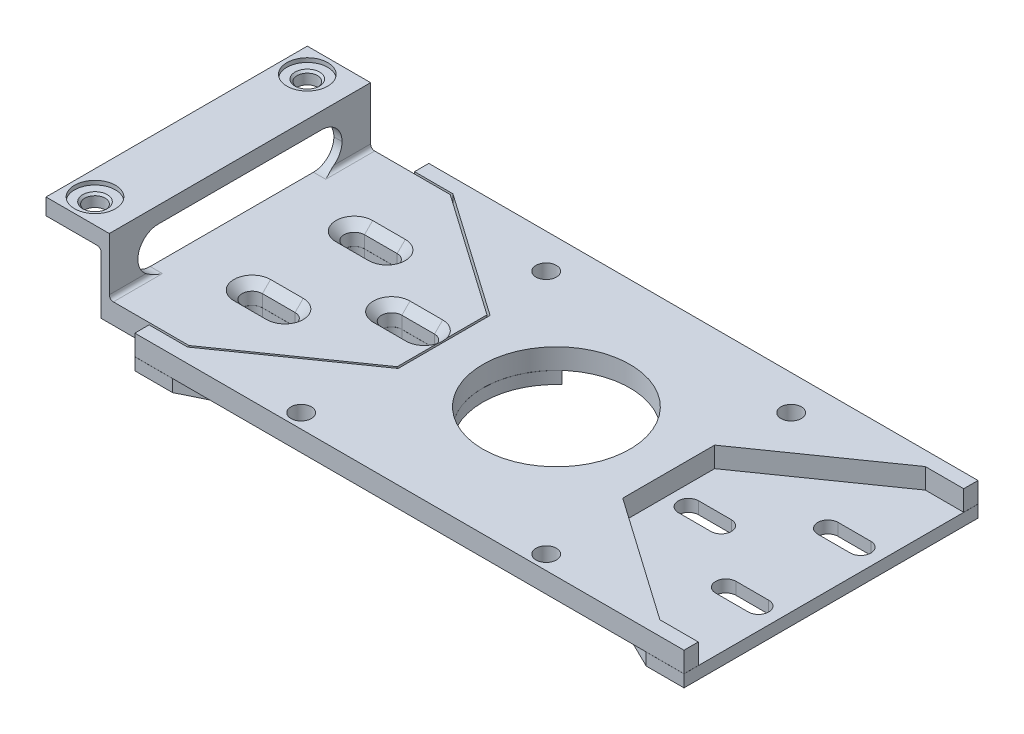
SolidWorks part; units mm, degrees
ref_plane "Front Plane" through (0, 0, 0) normal (0, 0, 1) x (1, 0, 0)
ref_plane "Top Plane" through (0, 0, 0) normal (0, 1, 0) x (1, 0, 0)
ref_plane "Right Plane" through (0, 0, 0) normal (1, 0, 0) x (0, 0, -1)
sketch "Sketch1" plane through (0, 0, 0) normal (0, 1, 0) x (1, 0, 0)
  line L0 (0, 40.64) -> (38.1, 13.9621)
  line L1 (-44.45, -40.64) -> (0, -40.64)
  line L2 (-44.45, -40.64) -> (-44.45, 40.64)
  line L3 (-44.45, 40.64) -> (0, 40.64)
  line L4 (38.1, -13.9621) -> (38.1, 13.9621)
  line L5 (-5.08, 19.05) -> (5.08, 19.05)
  line L6 (-5.08, 12.7) -> (5.08, 12.7)
  line L7 (0, -40.64) -> (38.1, -13.9621)
  line L8 (-5.08, -12.7) -> (5.08, -12.7)
  line L9 (-5.08, -19.05) -> (5.08, -19.05)
  line L10 (22.4163, 3.175) -> (32.5763, 3.175)
  line L11 (22.4163, -3.175) -> (32.5763, -3.175)
  circle A0 centre (-36.83, 33.02) radius 3.175
  circle A1 centre (-36.83, -33.02) radius 3.175
  arc A5 (5.08, 12.7) -> (5.08, 19.05) centre (5.08, 15.875) ccw
  arc A6 (-5.08, 19.05) -> (-5.08, 12.7) centre (-5.08, 15.875) ccw
  arc A7 (5.08, -19.05) -> (5.08, -12.7) centre (5.08, -15.875) ccw
  arc A8 (-5.08, -12.7) -> (-5.08, -19.05) centre (-5.08, -15.875) ccw
  arc A9 (22.4163, 3.175) -> (22.4163, -3.175) centre (22.4163, 0) ccw
  arc A10 (32.5763, -3.175) -> (32.5763, 3.175) centre (32.5763, 0) ccw
  point P0 (0, 0)
  point P4 (38.1, 0)
  dimension "D1" = 6.35
  dimension "D2" = 66.04
  dimension "D3" = 7.62
  dimension "D4" = 7.62
  dimension "D5" = 7.62
  dimension "D6" = 38.1
  dimension "D7" = 145
  dimension "D8" = 145
  dimension "D9" = 44.45
extrude "Boss-Extrude1" add sketch "Sketch1" along normal blind 6.35
sketch "Sketch10" plane through (0, 6.35, 0) normal (0, 1, 0) x (1, 0, 0)
  line L1 (-44.45, 40.64) -> (-24.765, 40.64)
  line L2 (-44.45, 40.64) -> (-44.45, -40.64)
  line L3 (-44.45, -40.64) -> (-24.765, -40.64)
  line L4 (-24.765, -40.64) -> (-24.765, 40.64)
  circle A0 centre (-36.83, -33.02) radius 3.175 construction
  circle A1 centre (-36.83, 33.02) radius 3.175 construction
  circle A2 centre (-36.83, -33.02) radius 3.175
  circle A3 centre (-36.83, 33.02) radius 3.175
  dimension "D1" = 19.685
extrude "Boss-Extrude4" add sketch "Sketch10" along normal blind 17.78
sketch "Sketch12" plane through (0, 0, 0) normal (0, -1, 0) x (1, 0, 0)
  line L0 (0, -40.64) -> (-44.45, -40.64) construction
  line L1 (-44.45, 40.64) -> (-27.305, 40.64)
  line L2 (-44.45, 40.64) -> (-44.45, -40.64)
  line L3 (-44.45, -40.64) -> (-27.305, -40.64)
  line L5 (-27.305, 40.64) -> (-27.305, -40.64)
  line L6 (-44.45, 40.64) -> (0, 40.64) construction
  point P9 (-22.225, 40.64)
  dimension "D1" = 5.08
extrude "Cut-Extrude5" cut sketch "Sketch12" against normal blind 12.7
sketch "Sketch14" plane through (0, 24.13, 0) normal (0, 1, 0) x (1, 0, 0)
  circle A0 centre (-36.83, 33.02) radius 6.35
  circle A1 centre (-36.83, -33.02) radius 6.35
  dimension "D1" = 12.7
extrude "Cut-Extrude9" cut sketch "Sketch14" against normal blind 1.27
chamfer "Chamfer2" distance 0.635 angle 45 2 edges at (-36.83, 22.86, -29.845) (-36.83, 22.86, 36.195)
sketch "Sketch15" plane through (-24.765, 0, 0) normal (1, 0, 0) x (0, 0, -1)
  line L0 (-31.75, 6.35) -> (-31.75, 19.05)
  line L1 (-40.64, 6.35) -> (-13.9621, 6.35) construction
  line L2 (-31.75, 19.05) -> (31.75, 19.05)
  line L3 (31.75, 19.05) -> (31.75, 6.35)
  line L4 (13.9621, 6.35) -> (40.64, 6.35) construction
  line L5 (31.75, 6.35) -> (-31.75, 6.35)
  line L6 (-40.64, 24.13) -> (-40.64, 6.35) construction
  line L7 (40.64, 24.13) -> (40.64, 6.35) construction
  line L8 (-40.64, 24.13) -> (40.64, 24.13) construction
  dimension "D1" = 8.89
  dimension "D2" = 8.89
  dimension "D3" = 5.08
extrude "Cut-Extrude10" cut sketch "Sketch15" against normal blind 36.576
sketch "Sketch16" plane through (0, 0, -40.64) normal (0, 0, -1) x (-1, 0, 0)
  line L0 (27.305, 12.7) -> (27.305, 19.05)
  line L1 (27.305, 19.05) -> (44.45, 19.05)
  line L2 (44.45, 24.13) -> (44.45, 12.7) construction
  line L3 (44.45, 19.05) -> (44.45, 12.7)
  line L4 (44.45, 12.7) -> (27.305, 12.7)
  dimension "D1" = 5.08
extrude "Cut-Extrude11" cut sketch "Sketch16" against normal blind 84.836
fillet "Fillet1" radius 1.27 4 edges at (-27.305, 19.05, 36.195) (-27.305, 19.05, -36.195) (-24.765, 6.35, 36.195) (-24.765, 6.35, -36.195)
fillet "Fillet2" radius 6.35 4 edges at (-25.4, 6.35, 31.75) (-25.4, 6.35, -31.75) (-26.67, 19.05, -31.75) (-26.67, 19.05, 31.75)
chamfer "Chamfer3" distance 2.54 angle 45 12 edges at (0, 6.35, 19.05) (8.255, 6.35, 15.875) (-8.255, 6.35, 15.875) (0, 6.35, 12.7) (27.4963, 6.35, 3.175) (35.7513, 6.35, 0) (19.2413, 6.35, 0) (27.4963, 6.35, -3.175) (0, 6.35, -12.7) (8.255, 6.35, -15.875) (-8.255, 6.35, -15.875) (0, 6.35, -19.05)
sketch "Sketch18" plane through (0, 6.35, 0) normal (0, 1, 0) x (1, 0, 0)
  line L0 (-24.765, 60.325) -> (-24.765, -60.325) construction
  line L1 (-24.765, 60.325) -> (172.085, 60.325) construction
  line L2 (-24.765, -60.325) -> (172.085, -60.325) construction
  line L3 (172.085, -60.325) -> (172.085, 60.325) construction
  line L4 (73.66, 60.325) -> (73.66, 34.925) construction
  line L5 (-24.765, 34.925) -> (35.56, 34.925) construction
  line L6 (35.56, 34.925) -> (111.76, 34.925) construction
  line L7 (35.56, 34.925) -> (35.56, -41.275) construction
  line L8 (-11.7475, 45.72) -> (-11.7475, 41.275)
  line L9 (-11.7475, -45.72) -> (159.0675, -45.72)
  line L10 (-23.495, -40.64) -> (0, -40.64) construction
  line L11 (-11.7475, 45.72) -> (159.0675, 45.72)
  line L12 (159.0675, 45.72) -> (159.0675, 41.275)
  line L47 (-11.7475, -41.275) -> (-11.7475, -45.72)
  line L48 (73.66, 45.72) -> (73.66, -45.72) construction
  line L49 (159.0675, -41.275) -> (147.1198, -41.275)
  line L50 (147.1198, -41.275) -> (108.585, -14.2927)
  line L51 (108.585, -14.2927) -> (108.585, -1.4663)
  line L52 (108.585, -1.4663) -> (108.585, 1.4663)
  line L53 (108.585, 1.4663) -> (108.585, 14.2927)
  line L54 (-23.495, -41.275) -> (0.2002, -41.275)
  line L55 (0.2002, -41.275) -> (38.735, -14.2927)
  line L56 (38.735, -1.4663) -> (38.735, 1.4663)
  line L57 (38.735, -14.2927) -> (38.735, -1.4663)
  line L58 (38.735, 1.4663) -> (38.735, 14.2927)
  line L59 (38.735, 14.2927) -> (0.2002, 41.275)
  line L60 (0.2002, 41.275) -> (-23.495, 41.275)
  line L61 (-11.7475, -41.275) -> (0.2002, -41.275)
  line L62 (0.2002, -41.275) -> (38.735, -14.2927)
  line L63 (38.735, -1.4663) -> (38.735, 1.4663)
  line L64 (38.735, -14.2927) -> (38.735, -1.4663)
  line L65 (38.735, 1.4663) -> (38.735, 14.2927)
  line L66 (38.735, 14.2927) -> (0.2002, 41.275)
  line L67 (0.2002, 41.275) -> (-11.7475, 41.275)
  line L68 (108.585, 14.2927) -> (147.1198, 41.275)
  line L69 (147.1198, 41.275) -> (159.0675, 41.275)
  line L70 (159.0675, 45.72) -> (159.0675, 41.275)
  line L71 (159.0675, -41.275) -> (159.0675, -45.72)
  line L72 (159.0675, -41.275) -> (159.0675, -45.72)
  circle A0 centre (35.56, 34.925) radius 3.175
  circle A1 centre (111.76, 34.925) radius 3.175
  circle A2 centre (35.56, -41.275) radius 3.175
  circle A3 centre (111.76, -41.275) radius 3.175
  point P2 (-24.765, 0)
  point P24 (73.66, -45.72)
  point P25 (73.66, 45.72)
  dimension "D5" = 6.35
  dimension "D6" = 76.2
  dimension "D10" = 6.35
  dimension "D1" = 120.65
  dimension "D2" = 196.85
  dimension "D3" = 60.325
  dimension "D4" = 25.4
  dimension "D7" = 76.2
  dimension "D8" = 5.08
  dimension "D9" = 5.08
  dimension "D11" = 76.2
  dimension "D12" = 76.2
  dimension "D14" = 11.7475
  dimension "D13" = 0.635
extrude "Boss-Extrude5" add sketch "Sketch18" against normal up to surface (6.35 mm away) separate body contours L71 L49 L50 L51 L52 L53 L68 L69 L12 L11 L8 L67 L66 L65 L63 L64 L62 L61 L47 L9 A3 A2 A1 A0 region at (73.66, 6.35, -0.0435) up to face at (3.5983, 0, 0)
sketch "Sketch19" plane through (0, 6.35, 0) normal (0, 1, 0) x (1, 0, 0)
  line L0 (108.585, -14.2927) -> (108.585, 14.2927) construction
  line L1 (-11.7475, 45.72) -> (159.0675, 45.72) construction
  circle A0 centre (73.66, 0) radius 22.86
  dimension "D1" = 34.925
  dimension "D3" = 45.72
  dimension "D2" = 45.72
extrude "Cut-Extrude12" cut sketch "Sketch19" against normal blind 25.4
sketch "Sketch20" plane through (0, 0, 0) normal (0, -1, 0) x (1, 0, 0)
  line L0 (-11.7475, 45.72) -> (-11.7475, -45.72)
  line L1 (-11.7475, -45.72) -> (159.0675, -45.72) construction
  line L2 (-11.7475, -45.72) -> (0, -45.72)
  line L6 (-11.7475, 45.72) -> (159.0675, 45.72) construction
  line L7 (0, 45.72) -> (-11.7475, 45.72)
  line L9 (0, -45.72) -> (73.66, -9.525)
  line L10 (0, 45.72) -> (73.66, 9.525)
  line L11 (159.0675, -45.72) -> (147.32, -45.72)
  line L12 (147.32, 45.72) -> (159.0675, 45.72)
  line L13 (159.0675, 45.72) -> (159.0675, -45.72)
  line L14 (147.32, -45.72) -> (73.66, -9.525)
  line L15 (147.32, 45.72) -> (73.66, 9.525)
  line L16 (5.08, -19.05) -> (-5.08, -19.05) construction
  line L17 (-5.08, -12.7) -> (5.08, -12.7) construction
  line L18 (32.5763, -3.175) -> (22.4163, -3.175) construction
  line L19 (22.4163, 3.175) -> (32.5763, 3.175) construction
  line L20 (5.08, 12.7) -> (-5.08, 12.7) construction
  line L21 (-5.08, 19.05) -> (5.08, 19.05) construction
  line L22 (5.08, -19.05) -> (-5.08, -19.05)
  line L23 (-5.08, -12.7) -> (5.08, -12.7)
  line L24 (32.5763, -3.175) -> (22.4163, -3.175)
  line L25 (22.4163, 3.175) -> (32.5763, 3.175)
  line L26 (5.08, 12.7) -> (-5.08, 12.7)
  line L27 (-5.08, 19.05) -> (5.08, 19.05)
  line L28 (73.66, -9.525) -> (73.66, -45.72) construction
  line L29 (142.24, -19.05) -> (152.4, -19.05)
  line L30 (152.4, -12.7) -> (142.24, -12.7)
  line L31 (124.9037, 3.175) -> (114.7437, 3.175)
  line L32 (114.7437, -3.175) -> (124.9037, -3.175)
  line L33 (152.4, 19.05) -> (142.24, 19.05)
  line L34 (142.24, 12.7) -> (152.4, 12.7)
  circle A0 centre (73.66, 0) radius 22.86 construction
  circle A1 centre (73.66, 0) radius 22.86 construction
  arc A2 (5.08, -19.05) -> (5.08, -12.7) centre (5.08, -15.875) ccw construction
  arc A3 (-5.08, -12.7) -> (-5.08, -19.05) centre (-5.08, -15.875) ccw construction
  arc A4 (32.5763, -3.175) -> (32.5763, 3.175) centre (32.5763, 0) ccw construction
  arc A5 (22.4163, 3.175) -> (22.4163, -3.175) centre (22.4163, 0) ccw construction
  arc A6 (-5.08, 19.05) -> (-5.08, 12.7) centre (-5.08, 15.875) ccw construction
  arc A7 (5.08, 12.7) -> (5.08, 19.05) centre (5.08, 15.875) ccw construction
  arc A8 (5.08, -19.05) -> (5.08, -12.7) centre (5.08, -15.875) ccw
  arc A9 (-5.08, -12.7) -> (-5.08, -19.05) centre (-5.08, -15.875) ccw
  arc A10 (32.5763, -3.175) -> (32.5763, 3.175) centre (32.5763, 0) ccw
  arc A11 (22.4163, 3.175) -> (22.4163, -3.175) centre (22.4163, 0) ccw
  arc A12 (-5.08, 19.05) -> (-5.08, 12.7) centre (-5.08, 15.875) ccw
  arc A13 (5.08, 12.7) -> (5.08, 19.05) centre (5.08, 15.875) ccw
  arc A14 (152.4, -12.7) -> (152.4, -19.05) centre (152.4, -15.875) cw
  arc A15 (142.24, -19.05) -> (142.24, -12.7) centre (142.24, -15.875) cw
  arc A16 (114.7437, -3.175) -> (114.7437, 3.175) centre (114.7437, 0) cw
  arc A17 (124.9037, 3.175) -> (124.9037, -3.175) centre (124.9037, 0) cw
  arc A18 (142.24, 12.7) -> (142.24, 19.05) centre (142.24, 15.875) cw
  arc A19 (152.4, 19.05) -> (152.4, 12.7) centre (152.4, 15.875) cw
  point P15 (0, 0)
  dimension "D1" = 19.05
extrude "Boss-Extrude6" add sketch "Sketch20" along normal blind 3.81 contours L9 L14 L11 L13 L12 L15 L10 L7 L0 L2
sketch "Sketch21" plane through (0, 0, 0) normal (0, 0, 1) x (1, 0, 0)
  line L0 (-11.7475, 0) -> (-11.7475, -0.0254)
  line L1 (-11.7475, -3.81) -> (-11.7475, 6.35) construction
  line L2 (-11.7475, -0.0254) -> (159.0675, -0.0254)
  line L3 (159.0675, -3.81) -> (159.0675, 6.35) construction
  line L4 (-11.7475, 0) -> (159.0675, 0)
  line L5 (159.0675, 0) -> (159.0675, -0.0254)
  dimension "D1" = 0.0254
extrude "Cut-Extrude13" cut sketch "Sketch21" against normal blind 56.896 and the other way blind 78.74
sketch "Sketch23" plane through (0, 6.35, 0) normal (0, 1, 0) x (1, 0, 0)
  line L0 (-5.08, -19.05) -> (5.08, -19.05) construction
  line L1 (5.08, -12.7) -> (-5.08, -12.7) construction
  line L2 (22.4163, -3.175) -> (32.5763, -3.175) construction
  line L3 (32.5763, 3.175) -> (22.4163, 3.175) construction
  line L4 (-5.08, 12.7) -> (5.08, 12.7) construction
  line L5 (5.08, 19.05) -> (-5.08, 19.05) construction
  line L6 (-5.08, -19.05) -> (5.08, -19.05)
  line L7 (5.08, -12.7) -> (-5.08, -12.7)
  line L8 (22.4163, -3.175) -> (32.5763, -3.175)
  line L9 (32.5763, 3.175) -> (22.4163, 3.175)
  line L10 (-5.08, 12.7) -> (5.08, 12.7)
  line L11 (5.08, 19.05) -> (-5.08, 19.05)
  line L12 (73.66, 45.72) -> (73.66, -45.72) construction
  line L13 (-11.7475, 45.72) -> (159.0675, 45.72) construction
  line L14 (-11.7475, -45.72) -> (159.0675, -45.72) construction
  line L15 (142.24, -12.7) -> (152.4, -12.7)
  line L16 (152.4, -19.05) -> (142.24, -19.05)
  line L17 (114.7437, 3.175) -> (124.9037, 3.175)
  line L18 (124.9037, -3.175) -> (114.7437, -3.175)
  line L19 (142.24, 19.05) -> (152.4, 19.05)
  line L20 (152.4, 12.7) -> (142.24, 12.7)
  arc A0 (-5.08, -12.7) -> (-5.08, -19.05) centre (-5.08, -15.875) ccw construction
  arc A1 (5.08, -19.05) -> (5.08, -12.7) centre (5.08, -15.875) ccw construction
  arc A2 (32.5763, -3.175) -> (32.5763, 3.175) centre (32.5763, 0) ccw construction
  arc A3 (22.4163, 3.175) -> (22.4163, -3.175) centre (22.4163, 0) ccw construction
  arc A4 (-5.08, 19.05) -> (-5.08, 12.7) centre (-5.08, 15.875) ccw construction
  arc A5 (5.08, 12.7) -> (5.08, 19.05) centre (5.08, 15.875) ccw construction
  arc A6 (-5.08, -12.7) -> (-5.08, -19.05) centre (-5.08, -15.875) ccw
  arc A7 (5.08, -19.05) -> (5.08, -12.7) centre (5.08, -15.875) ccw
  arc A8 (32.5763, -3.175) -> (32.5763, 3.175) centre (32.5763, 0) ccw
  arc A9 (22.4163, 3.175) -> (22.4163, -3.175) centre (22.4163, 0) ccw
  arc A10 (-5.08, 19.05) -> (-5.08, 12.7) centre (-5.08, 15.875) ccw
  arc A11 (5.08, 12.7) -> (5.08, 19.05) centre (5.08, 15.875) ccw
  arc A12 (152.4, -12.7) -> (152.4, -19.05) centre (152.4, -15.875) cw
  arc A13 (142.24, -19.05) -> (142.24, -12.7) centre (142.24, -15.875) cw
  arc A14 (124.9037, 3.175) -> (124.9037, -3.175) centre (124.9037, 0) cw
  arc A15 (114.7437, -3.175) -> (114.7437, 3.175) centre (114.7437, 0) cw
  arc A16 (152.4, 19.05) -> (152.4, 12.7) centre (152.4, 15.875) cw
  arc A17 (142.24, 12.7) -> (142.24, 19.05) centre (142.24, 15.875) cw
extrude "Cut-Extrude15" cut sketch "Sketch23" against normal blind 56.896
sketch "Sketch24" plane through (0, 6.35, 0) normal (0, 1, 0) x (1, 0, 0)
  circle A0 centre (73.66, 0) radius 22.86
extrude "Cut-Extrude16" cut sketch "Sketch24" against normal blind 56.896
equation "\"0.05n\"=0.0937008"
